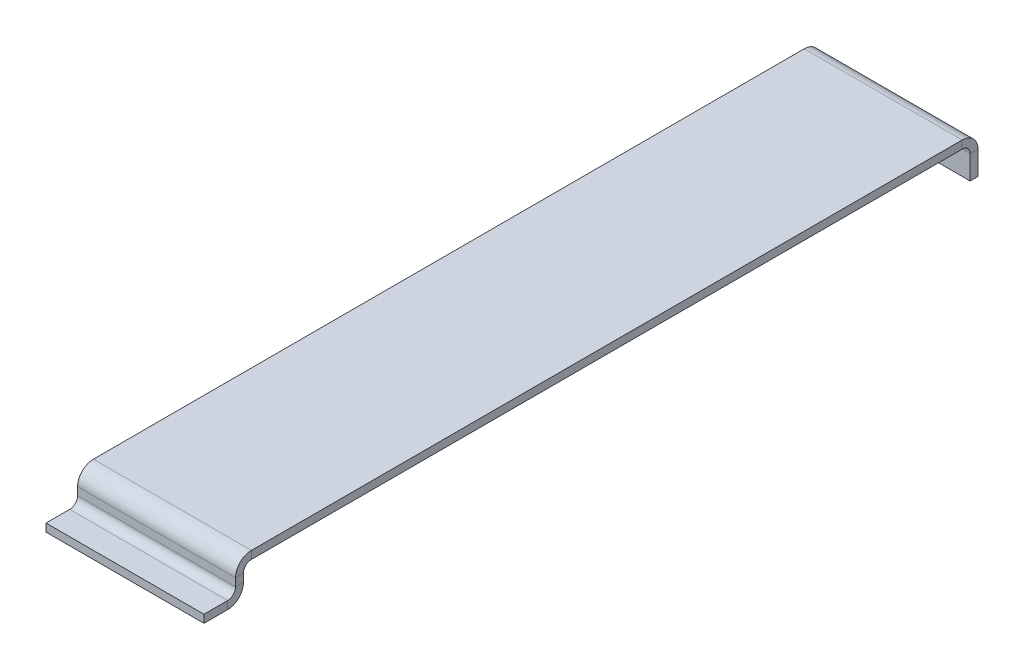
SolidWorks part; units mm, degrees
note: The reader was unsure of these and kept them because the rebuilt part matched: flange length of "Aresta-Flange1", "Aresta-Flange4".
ref_plane "Plano frontal" through (0, 0, 0) normal (0, 0, 1) x (1, 0, 0)
ref_plane "Plano superior" through (0, 0, 0) normal (0, 1, 0) x (1, 0, 0)
ref_plane "Plano direito" through (0, 0, 0) normal (1, 0, 0) x (0, 0, -1)
sketch "Esboço1" plane through (0, 0, 0) normal (0, 1, 0) x (1, 0, 0)
  line L1 (-20, 90) -> (20, 90)
  line L2 (-20, 90) -> (-20, -90)
  line L3 (-20, -90) -> (20, -90)
  line L4 (20, 90) -> (20, -90)
  line L5 (-20, 90) -> (20, -90) construction
  line L6 (-20, -90) -> (20, 90) construction
  point P0 (0, 0)
  dimension "D1" = 180
  dimension "D2" = 40
base flange "Flange-base1" sketch "Esboço1" thickness 2 reverse thickness direction no parameters "D1"=10
edge flange "Aresta-Flange1" sketch "Esboço8" flange profiles "Esboço8", "Esboço17" flange angle 90 flange length 10 flange position bend outside bend radius 2 thickness 2 relief rectangular parameters "D6"=10, "D8"=1
sketch "Esboço8" plane through (0, -2, 90) normal (0, 0, 1) x (-1, 0, 0)
  line L2 (-20, 0) -> (-20, 8)
  line L3 (-20, 8) -> (20, 8)
  line L4 (20, 8) -> (20, 0)
  line L5 (20, 0) -> (-20, 0) construction
  line L6 (20, 0) -> (-20, 0)
sketch "Esboço17" plane through (0, -2, -90) normal (0, 0, -1) x (1, 0, 0)
  line L0 (20, 0) -> (-20, 0) construction
  line L1 (20, 0) -> (-20, 0)
  line L2 (-20, 0) -> (-20, 8)
  line L3 (-20, 8) -> (20, 8)
  line L4 (20, 8) -> (20, 0)
bend "DobradeAresta1" bend radius 2 bend angle 90 parameters "D5"=1
bend "DobradeAresta5" bend radius 2 bend angle 90 parameters "D5"=3
edge flange "Aresta-Flange4" sketch "Esboço13" flange angle 90 flange length 10 flange position material inside bend radius 2 thickness 2 relief rectangular parameters "D6"=10
sketch "Esboço13" plane through (0, -10, 94) normal (0, -1, 0) x (1, 0, 0)
  line L0 (-20, 0) -> (20, 0) construction
  line L1 (-20, 0) -> (20, 0)
  line L2 (-20, 0) -> (-20, 8)
  line L3 (-20, 8) -> (20, 8)
  line L4 (20, 8) -> (20, 0)
bend "DobradeAresta4" bend radius 2 bend angle 90 parameters "D5"=2
sketch "Curva-Linhas1" [suppressed] plane through (0, 0, 0) normal (0, 1, 0) x (1, 0, 0)
sketch "Caixa delimitadora1" [suppressed] plane through (0, 0, 0) normal (0, 1, 0) x (1, 0, 0)
sheet metal parameters "Chapa metálica1" thickness 2 parameters "D1"=10
flat pattern "Padrão-Plano1" [suppressed]
sketch "Curva-Linhas2" plane through (0, 0, 0) normal (0, 1, 0) x (1, 0, 0)
sketch3d "Caixa delimitadora2" [suppressed]
  line L0 (20, 90, 0) -> (20, -90, 0) construction
  line L1 (-20, 90, 0) -> (-20, -90, 0) construction
  line L2 (20, 90, 0) -> (-20, 90, 0) construction
  line L3 (20, -90, 0) -> (-20, -90, 0) construction
sheet metal parameters "Chapa metálica2" thickness 2 parameters "D1"=10
flat pattern "Padrão-Plano1" [suppressed]
sketch "Curva-Linhas2" plane through (0, 0, 0) normal (0, 1, 0) x (1, 0, 0)
  line L0 (-20, -92.3562) -> (20, -92.3562) construction
  line L1 (-20, -92.3562) -> (20, -92.3562) construction
sketch3d "Caixa delimitadora2" [suppressed]
  line L0 (-20, 90, 0) -> (-20, -98.7124, 0) construction
  line L1 (20, 90, 0) -> (20, -98.7124, 0) construction
  line L2 (-20, 90, 0) -> (20, 90, 0) construction
  line L3 (-20, -98.7124, 0) -> (20, -98.7124, 0) construction
bend of the flat pattern "Planificar-<DobradeAresta1>1"
bend of the flat pattern "Planificar-<DobradeAresta5>1"
sheet metal parameters "Chapa metálica3" thickness 2 parameters "D1"=10
flat pattern "Padrão-Plano1"
sketch "Curva-Linhas2" plane through (0, 0, 0) normal (0, 1, 0) x (1, 0, 0)
  line L0 (-20, -92.3562) -> (20, -92.3562) construction
  line L1 (-20, -92.3562) -> (20, -92.3562) construction
  line L2 (-20, -99.0686) -> (20, -99.0686) construction
  line L3 (-20, -99.0686) -> (20, -99.0686) construction
  line L4 (20, 92.3562) -> (-20, 92.3562) construction
  line L5 (20, 92.3562) -> (-20, 92.3562) construction
sketch3d "Caixa delimitadora2" [suppressed]
  line L0 (-20, 100.7124, 0) -> (-20, -107.4248, 0) construction
  line L1 (20, 100.7124, 0) -> (20, -107.4248, 0) construction
  line L2 (-20, 100.7124, 0) -> (20, 100.7124, 0) construction
  line L3 (-20, -107.4248, 0) -> (20, -107.4248, 0) construction
bend of the flat pattern "Planificar-<DobradeAresta1>1"
bend of the flat pattern "Planificar-<DobradeAresta4>1"
bend of the flat pattern "Planificar-<DobradeAresta5>2"
